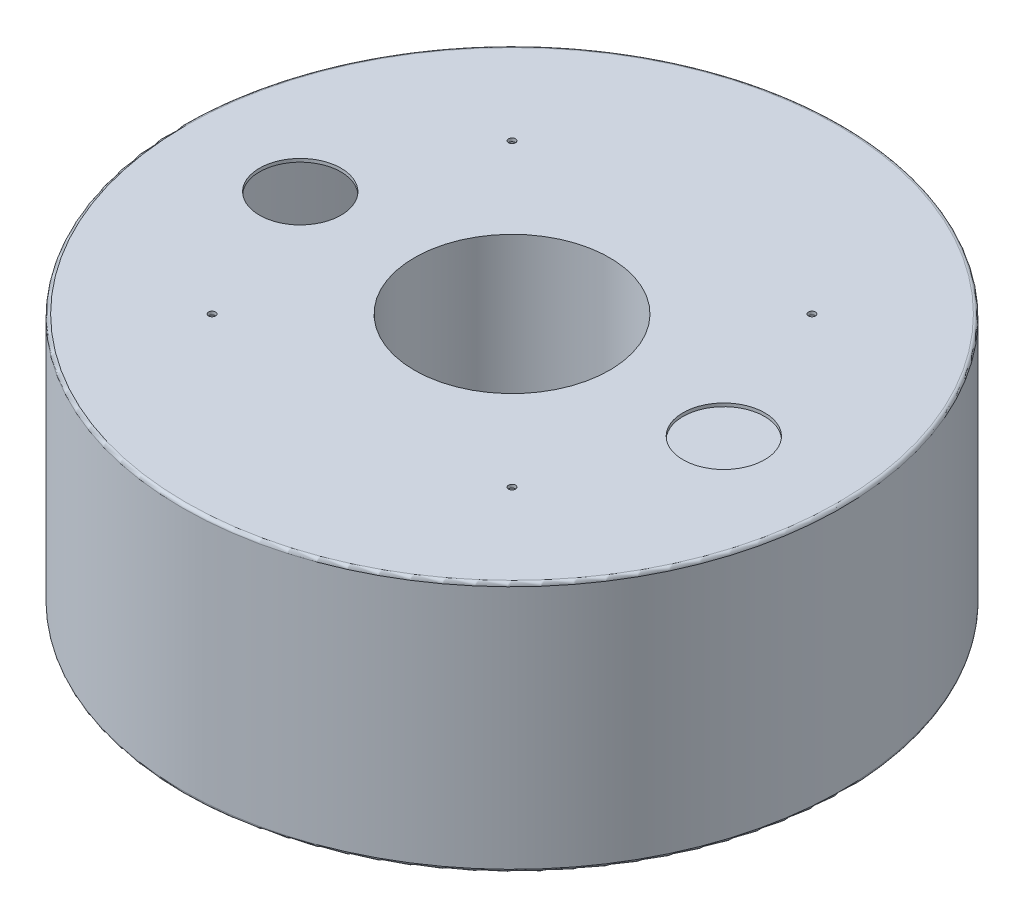
SolidWorks part; units mm, degrees
material "2014 Alloy"
ref_plane "Front Plane" through (0, 0, 0) normal (0, 0, 1) x (1, 0, 0)
ref_plane "Top Plane" through (0, 0, 0) normal (0, 1, 0) x (1, 0, 0)
ref_plane "Right Plane" through (0, 0, 0) normal (1, 0, 0) x (0, 0, -1)
sketch "Sketch9" plane through (0, 0, 0) normal (0, 1, 0) x (1, 0, 0)
  circle A0 centre (0, 0) radius 2000
extrude "Boss-Extrude5" add sketch "Sketch9" along normal blind 1500
sketch "Sketch10" plane through (0, 1500, 0) normal (0, 1, 0) x (1, 0, 0)
  circle A0 centre (0, 0) radius 598.217
extrude "Cut-Extrude3" cut sketch "Sketch10" against normal blind 1500
shell "Shell6" thickness 20 removed face at (0, 0, 598.217) outward yes
sketch "Sketch11" plane through (0, 1520, 0) normal (0, 1, 0) x (1, 0, 0)
  circle A0 centre (0, 0) radius 598.217
extrude "Boss-Extrude6" add sketch "Sketch11" against normal through all
sketch "Sketch13" plane through (0, 1520, 0) normal (0, 1, 0) x (1, 0, 0)
  circle A0 centre (0, 0) radius 618.217
extrude "Boss-Extrude7" add sketch "Sketch13" against normal through all
sketch "Sketch14" plane through (0, 1520, 0) normal (0, 1, 0) x (1, 0, 0)
  circle A0 centre (0, 0) radius 598.217
extrude "Cut-Extrude5" cut sketch "Sketch14" against normal through all
fillet "Fillet2" radius 20 2 edges at (0, 1520, 2020) (0, -20, 2020)
sketch "Sketch16" plane through (0, 1520, 0) normal (0, 1, 0) x (1, 0, 0)
  circle A0 centre (-1298.217, 0) radius 250
  circle A1 centre (1298.217, 0) radius 250
  dimension "D1" = 2
extrude "Cut-Extrude6" cut sketch "Sketch16" against normal blind 547 and the other way through all
sketch "Sketch17" plane through (0, 1520, 0) normal (0, 1, 0) x (1, 0, 0)
  circle A0 centre (919.2388, 919.2388) radius 21.463
  circle A1 centre (919.2388, -919.2388) radius 21.463
  circle A2 centre (-919.2388, -919.2388) radius 21.463
  circle A3 centre (-919.2388, 919.2388) radius 21.463
  dimension "D1" = 4
extrude "Cut-Extrude9" cut sketch "Sketch17" against normal blind 547
